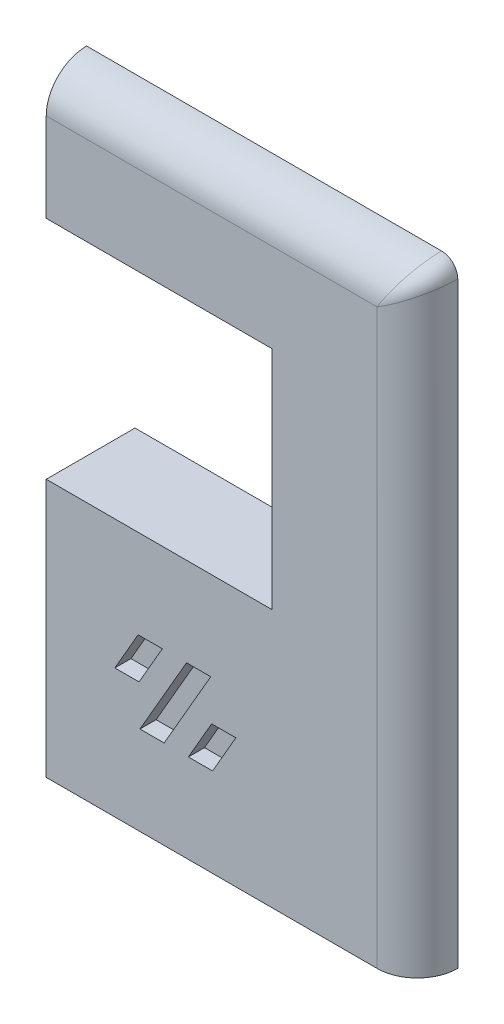
SolidWorks part; units mm, degrees
ref_plane "Front Plane" through (0, 0, 0) normal (0, 0, 1) x (1, 0, 0)
ref_plane "Top Plane" through (0, 0, 0) normal (0, 1, 0) x (1, 0, 0)
ref_plane "Right Plane" through (0, 0, 0) normal (1, 0, 0) x (0, 0, -1)
sketch "Sketch1" plane through (0, 0, 0) normal (0, 0, 1) x (1, 0, 0)
  line L1 (-14.899, 13.3838) -> (5.101, 13.3838)
  line L2 (-14.899, 13.3838) -> (-14.899, -21.6162)
  line L3 (-14.899, -21.6162) -> (5.101, -21.6162)
  line L4 (5.101, 13.3838) -> (5.101, -21.6162)
  dimension "D1" = 20
  dimension "D2" = 35
extrude "Boss-Extrude1" add sketch "Sketch1" along normal blind 3
fillet "Fillet1" radius 1 1 edges at (5.101, 13.3838, 1.5)
sketch "Sketch2" plane through (0, 0, 3) normal (0, 0, 1) x (1, 0, 0)
  line L0 (-14.899, 13.3838) -> (-14.899, -21.6162) construction
  line L1 (-14.899, -5.6162) -> (-0.899, -5.6162)
  line L2 (-14.899, -5.6162) -> (-14.899, 8.3838)
  line L3 (-14.899, 8.3838) -> (-0.899, 8.3838)
  line L4 (-0.899, -5.6162) -> (-0.899, 8.3838)
  line L5 (-14.899, -21.6162) -> (5.101, -21.6162) construction
  dimension "D1" = 16
  dimension "D2" = 14
  dimension "D3" = 14
extrude "Cut-Extrude1" cut sketch "Sketch2" against normal through all and the other way blind 12.5
sketch "Sketch4" plane through (0, 0, 3) normal (0, 0, 1) x (1, 0, 0)
  line L0 (4.101, 13.3838) -> (-14.899, 13.3838) construction
  line L1 (-14.899, 16.3838) -> (8.101, 16.3838)
  line L2 (-14.899, 16.3838) -> (-14.899, -21.6162)
  line L3 (-14.899, -21.6162) -> (8.101, -21.6162)
  line L4 (8.101, 16.3838) -> (8.101, -21.6162)
  line L5 (5.101, -21.6162) -> (5.101, 12.3838) construction
  dimension "D1" = 3
  dimension "D2" = 3
  dimension "D3" = 38
extrude "Boss-Extrude2" add sketch "Sketch4" along normal blind 2.5
fillet "Fillet2" radius 1 1 edges at (8.101, 16.3838, 4.25)
sketch "Sketch5" plane through (0, 0, 3) normal (0, 0, -1) x (-1, 0, 0)
  line L1 (0.899, 8.3838) -> (14.899, 8.3838)
  line L2 (0.899, 8.3838) -> (0.899, -5.6162)
  line L3 (0.899, -5.6162) -> (14.899, -5.6162)
  line L4 (14.899, 8.3838) -> (14.899, -5.6162)
extrude "Cut-Extrude2" cut sketch "Sketch5" against normal blind 2.5
fillet "Fillet3" radius 2.5 3 edges at (8.101, -3.1162, 5.5) (7.8081, 16.0909, 5.5) (-3.899, 16.3838, 5.5)
sketch "Sketch6" plane through (0, 0, 0) normal (0, 0, -1) x (-1, 0, 0)
  line L0 (14.899, -21.6162) -> (-5.101, -21.6162) construction
  line L1 (0.899, -5.6162) -> (0.899, 8.3838) construction
  circle A0 centre (-2.101, 5.3838) radius 1.4
  dimension "D1" = 2.8
  dimension "D2" = 27
  dimension "D3" = 3
sketch "Sketch7" plane through (0, 0, 0) normal (0, 0, -1) x (-1, 0, 0)
  line L0 (14.899, -5.6162) -> (14.899, -21.6162) construction
  line L1 (14.899, -21.6162) -> (-5.101, -21.6162) construction
  circle A0 centre (2.899, -13.6162) radius 3.065
  dimension "D1" = 6.13
  dimension "D2" = 12
  dimension "D3" = 8
extrude "Cut-Extrude4" cut sketch "Sketch7" against normal blind 3.1
sketch "Sketch12" plane through (0, 0, 5.5) normal (0, 0, 1) x (1, 0, 0)
  line L0 (-9.2056, -11.1162) -> (-7.7056, -11.1162)
  line L1 (-7.7056, -11.1162) -> (-9.149, -13.6162)
  line L2 (-9.149, -13.6162) -> (-10.649, -13.6162)
  line L3 (-10.649, -13.6162) -> (-9.2056, -11.1162)
  line L4 (-6.2056, -11.1162) -> (-4.7056, -11.1162)
  line L5 (-4.7056, -11.1162) -> (-7.5924, -16.1162)
  line L6 (-7.5924, -16.1162) -> (-9.0924, -16.1162)
  line L7 (-9.0924, -16.1162) -> (-6.2056, -11.1162)
  line L8 (-6.0924, -16.1162) -> (-4.5924, -16.1162)
  line L9 (-4.5924, -16.1162) -> (-3.149, -13.6162)
  line L10 (-3.149, -13.6162) -> (-4.649, -13.6162)
  line L11 (-4.649, -13.6162) -> (-6.0924, -16.1162)
  line L13 (-0.899, -5.6162) -> (-14.899, -5.6162) construction
  line L14 (-14.899, -5.6162) -> (-14.899, -21.6162) construction
  dimension "D1" = 1.5
  dimension "D2" = 1.5
  dimension "D3" = 1.5
  dimension "D4" = 1.5
  dimension "D5" = 1.5
  dimension "D6" = 1.5
  dimension "D7" = 5
  dimension "D10" = 1.5
  dimension "D11" = 1.5
  dimension "D12" = 8
  dimension "D13" = 4.25
extrude "Cut-Extrude5" cut sketch "Sketch12" against normal blind 1
extrude "Boss-Extrude3" add sketch "Sketch6" along normal blind 1.75
fillet "Fillet5" radius 1 1 edges at (0.701, 5.3838, -1.75)
